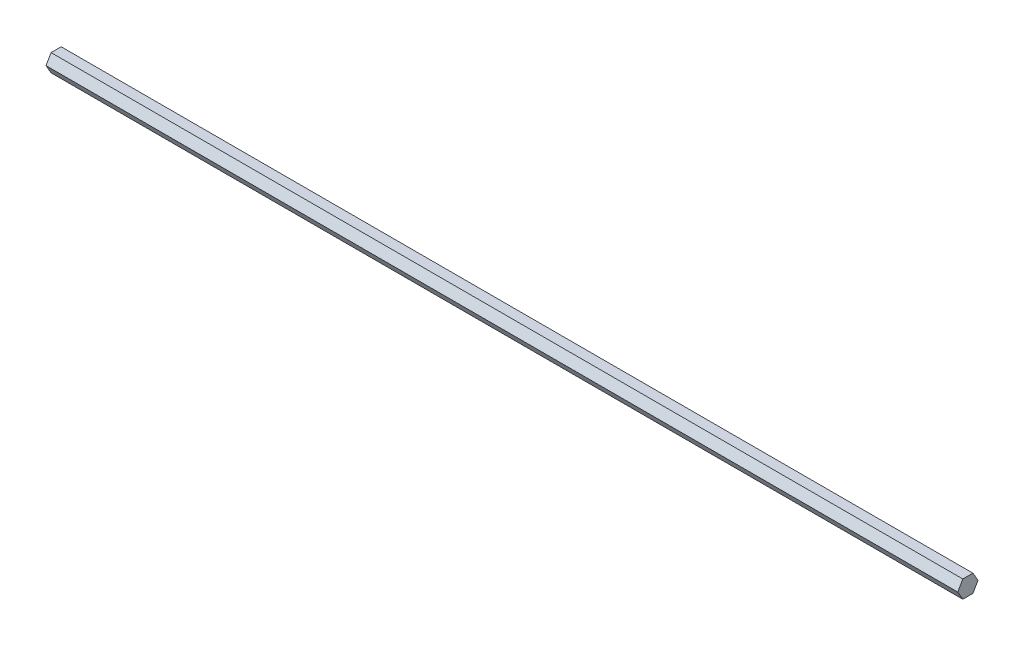
SolidWorks part; units mm, degrees
ref_plane "Front Plane" through (0, 0, 0) normal (0, 0, 1) x (1, 0, 0)
ref_plane "Top Plane" through (0, 0, 0) normal (0, 1, 0) x (1, 0, 0)
ref_plane "Right Plane" through (0, 0, 0) normal (1, 0, 0) x (0, 0, -1)
sketch "Sketch1" plane through (0, 0, 0) normal (1, 0, 0) x (0, 0, -1)
  line L1 (7.3323, 0) -> (3.6662, 6.35)
  line L2 (3.6662, 6.35) -> (-3.6662, 6.35)
  line L3 (-3.6662, 6.35) -> (-7.3323, 0)
  line L4 (-7.3323, 0) -> (-3.6662, -6.35)
  line L5 (-3.6662, -6.35) -> (3.6662, -6.35)
  line L6 (3.6662, -6.35) -> (7.3323, 0)
  circle A0 centre (0, 0) radius 6.35 construction
  dimension "D1" = 12.7
extrude "Boss-Extrude1" add sketch "Sketch1" along normal blind 660.4
